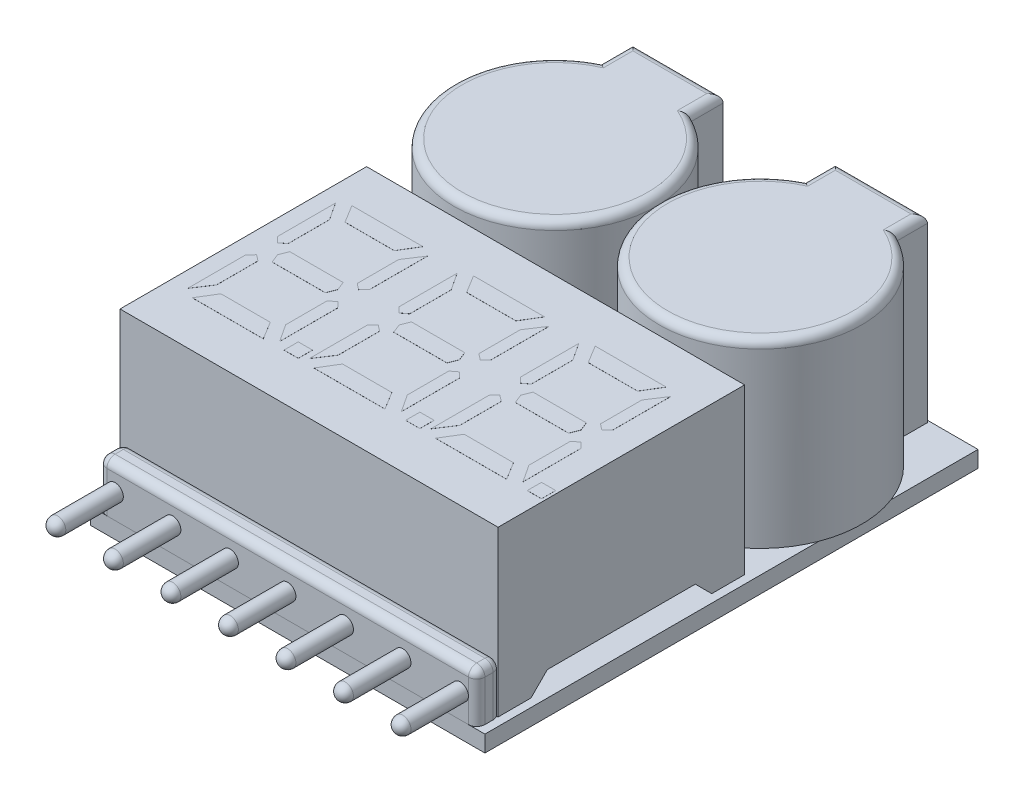
SolidWorks part; units mm, degrees
ref_plane "Ön Düzlem" through (0, 0, 0) normal (0, 0, 1) x (1, 0, 0)
ref_plane "Üst Düzlem" through (0, 0, 0) normal (0, 1, 0) x (1, 0, 0)
ref_plane "Sağ Düzlem" through (0, 0, 0) normal (1, 0, 0) x (0, 0, -1)
sketch "Çizim1" plane through (0, 0, 0) normal (0, 1, 0) x (1, 0, 0)
  line L1 (12, -20) -> (-12, -20)
  line L2 (12, -20) -> (12, 20)
  line L3 (12, 20) -> (-12, 20)
  line L4 (-12, -20) -> (-12, 20)
  line L5 (12, -20) -> (-12, 20) construction
  line L6 (12, 20) -> (-12, -20) construction
  point P0 (0, 0)
  dimension "D1" = 40
  dimension "D2" = 24
extrude "Yükseklik-Ekstrüzyon1" add sketch "Çizim1" along normal blind 1
sketch "Çizim2" plane through (0, 1, 0) normal (0, 1, 0) x (1, 0, 0)
  line L1 (-11.5, -10) -> (11.5, -10)
  line L2 (-11.5, -10) -> (-11.5, -8.5)
  line L3 (-11.5, -8.5) -> (11.5, -8.5)
  line L4 (11.5, -10) -> (11.5, -8.5)
  line L5 (-12, 20) -> (-12, -20) construction
  line L6 (12, -20) -> (12, 20) construction
  line L8 (12, 20) -> (-12, 20) construction
  dimension "D1" = 0.5
  dimension "D2" = 0.5
  dimension "D3" = 1.5
  dimension "D4" = 28.5
  dimension "D5" = 1.5
extrude "Yükseklik-Ekstrüzyon2" add sketch "Çizim2" along normal blind 3 separate body
sketch "Çizim3" plane through (0, 0, 10) normal (0, 0, 1) x (1, 0, 0)
  line L0 (-11.5, 2.5) -> (11.5, 2.5) construction
  line L1 (-11.5, 4) -> (-11.5, 1) construction
  line L2 (11.5, 4) -> (11.5, 1) construction
  line L3 (-8, 2.5) -> (15, 2.5) construction
  line L4 (-4.5, 2.5) -> (18.5, 2.5) construction
  line L5 (-1, 2.5) -> (22, 2.5) construction
  line L6 (-15, 2.5) -> (8, 2.5) construction
  line L7 (-18.5, 2.5) -> (4.5, 2.5) construction
  line L8 (-22, 2.5) -> (1, 2.5) construction
  circle A0 centre (0, 2.5) radius 0.5
  circle A1 centre (3.5, 2.5) radius 0.5
  circle A2 centre (7, 2.5) radius 0.5
  circle A3 centre (10.5, 2.5) radius 0.5
  circle A4 centre (-3.5, 2.5) radius 0.5
  circle A5 centre (-7, 2.5) radius 0.5
  circle A6 centre (-10.5, 2.5) radius 0.5
  dimension "D1" = 1
  dimension "D2" = 4
  dimension "D3" = 4
extrude "Yükseklik-Ekstrüzyon3" add sketch "Çizim3" along normal blind 4
sketch "Çizim4" plane through (0, 1, 0) normal (0, 1, 0) x (1, 0, 0)
  line L0 (12, 20) -> (-12, 20) construction
  line L1 (-11.5, -8.7) -> (11.5, -8.7)
  line L2 (-11.5, -8.7) -> (-11.5, 6.3)
  line L3 (-11.5, 6.3) -> (11.5, 6.3)
  line L4 (11.5, -8.7) -> (11.5, 6.3)
  line L5 (-11.5, -8.7) -> (11.5, 6.3) construction
  line L6 (-11.5, 6.3) -> (11.5, -8.7) construction
  line L7 (-12, 20) -> (-12, -20) construction
  line L8 (12, -20) -> (12, 20) construction
  point P0 (0, -1.2)
  dimension "D1" = 15
  dimension "D2" = 23
  dimension "D3" = 13.7
extrude "Yükseklik-Ekstrüzyon4" add sketch "Çizim4" along normal blind 10
sketch "Çizim5" plane through (0, 1, 0) normal (0, 1, 0) x (1, 0, 0)
  line L0 (12, 20) -> (-12, 20) construction
  line L7 (3.4483, 17.9999) -> (3.4483, 19.8699)
  line L9 (-9, 18.026) -> (-9, 20)
  line L10 (-9, 20) -> (-3.5, 20)
  line L11 (-3.5, 18.026) -> (-3.5, 20)
  line L14 (9.0517, 19.8699) -> (3.4483, 19.8699)
  line L15 (9.0517, 17.9999) -> (9.0517, 19.8699)
  arc A0 (-9, 18.026) -> (-3.5, 18.026) centre (-6.25, 12.5175) ccw
  arc A1 (3.4483, 17.9999) -> (9.0517, 17.9999) centre (6.25, 12.5175) ccw
  point P9 (0, 6.418)
  point P16 (-6.25, 18.6743)
  dimension "D1" = 5.5
  dimension "D2" = 1.974
extrude "Yükseklik-Ekstrüzyon10" add sketch "Çizim5" along normal blind 11
sketch "Çizim6" plane through (-11.5, 0, 0) normal (-1, 0, 0) x (0, 0, 1)
  line L0 (6.7, 1) -> (5.7, 2)
  line L1 (-6.3, 1) -> (8.7, 1) construction
  line L2 (5.7, 2) -> (-3.3, 2)
  line L3 (-3.3, 2) -> (-4.3, 1)
  line L4 (6.7, 1) -> (-4.3, 1)
  point P4 (1.2, 1)
  point P7 (1.2, 2)
  dimension "D1" = 2
  dimension "D2" = 1
  dimension "D3" = 135
extrude "Kes-Ekstrüzyon2" cut sketch "Çizim6" against normal blind 40
sketch "Çizim7" plane through (0, 0, 8.7) normal (0, 0, 1) x (1, 0, 0)
  line L0 (-9.5, 1) -> (-8.386, 2)
  line L2 (-12, 1) -> (12, 1) construction
  line L3 (-8.386, 2) -> (8.386, 2)
  line L4 (11.5, 11) -> (11.5, 1) construction
  line L5 (-11.5, 11) -> (-11.5, 1) construction
  line L6 (-11.5, 6) -> (11.5, 6) construction
  line L8 (8.386, 2) -> (9.2837, 1)
  line L9 (-11.5, 1) -> (11.5, 1) construction
  line L10 (-9.5, 1) -> (9.2837, 1)
  line L14 (0, 6) -> (0, 11) construction
  line L15 (-11.5, 11) -> (11.5, 11) construction
  point P5 (0, 2)
  dimension "D1" = 23
  dimension "D2" = 2
  dimension "D3" = 1
extrude "Kes-Ekstrüzyon3" cut sketch "Çizim7" against normal blind 20
fillet "Radyus1" radius 0.5 8 edges at (11.5, 4, 9.25) (0, 4, 10) (11.5, 2.5, 10) (-11.5, 4, 9.25) (-11.5, 2.5, 10) (-11.5, 2.5, 8.5) (0, 4, 8.5) (11.5, 2.5, 8.5)
fillet "Radyus2" radius 0.5 8 edges at (3.4483, 12, -18.9349) (6.25, 12, -19.8699) (9.0517, 12, -18.9349) (6.25, 12, -6.3607) (-9, 12, -19.013) (-6.25, 12, -20) (-3.5, 12, -19.013) (-6.25, 12, -6.3607)
sketch "Çizim8" plane through (0, 11, 0) normal (0, 1, 0) x (1, 0, 0)
  line L0 (-9.3462, -0.5211) -> (-6.1062, -0.5211)
  line L1 (-6.2265, -4.8359) -> (-9.2259, -4.8359)
  line L2 (-9.2259, -4.8359) -> (-9.8862, -5.9159)
  line L3 (-9.8283, -4.498) -> (-10.5232, -5.556)
  line L4 (-10.5232, -5.556) -> (-10.5232, -2.0259)
  line L5 (-9.8283, -4.498) -> (-9.8283, -1.9771)
  line L6 (-10.5232, -2.0259) -> (-10.198, -1.693)
  line L7 (-10.198, -1.693) -> (-9.8283, -1.9771)
  line L8 (-9.3462, -1.6011) -> (-6.1062, -1.6011)
  line L9 (-9.8862, -5.9159) -> (-5.5662, -5.9159)
  line L10 (-4.3393, -5.0178) -> (-3.4753, -5.0178)
  line L11 (-4.3393, -5.0178) -> (-4.3393, -5.8818)
  line L12 (-4.3393, -5.8818) -> (-3.4753, -5.8818)
  line L13 (-9.5601, -1.0611) -> (-9.3462, -0.5211)
  line L14 (-3.4753, -5.0178) -> (-3.4753, -5.8818)
  line L15 (-5.8922, -1.0611) -> (-6.1062, -0.5211)
  line L16 (-5.2544, -1.693) -> (-5.6241, -1.9771)
  line L17 (-4.9291, -2.0259) -> (-5.2544, -1.693)
  line L18 (-5.6241, -4.498) -> (-5.6241, -1.9771)
  line L19 (-4.9291, -5.556) -> (-4.9291, -2.0259)
  line L20 (-5.6241, -4.498) -> (-4.9291, -5.556)
  line L21 (-6.2265, -4.8359) -> (-5.5662, -5.9159)
  line L23 (-2.4862, -5.9159) -> (1.8338, -5.9159)
  line L24 (-5.5662, 3.7938) -> (-9.8862, 3.7938)
  line L25 (4.9138, -5.9159) -> (9.2338, -5.9159)
  line L26 (-9.2259, 2.7138) -> (-6.2265, 2.7138)
  line L27 (-6.2265, 2.7138) -> (-5.5662, 3.7938)
  line L28 (-5.6241, 2.3758) -> (-4.9291, 3.4339)
  line L29 (-4.9291, 3.4339) -> (-4.9291, -0.0963)
  line L30 (-5.6241, 2.3758) -> (-5.6241, -0.1451)
  line L31 (-4.9291, -0.0963) -> (-5.2544, -0.4291)
  line L32 (-5.2544, -0.4291) -> (-5.6241, -0.1451)
  line L33 (1.1735, -4.8359) -> (-1.8259, -4.8359)
  line L34 (-5.8922, -1.0611) -> (-6.1062, -1.6011)
  line L35 (-9.5601, -1.0611) -> (-9.3462, -1.6011)
  line L36 (-1.8259, -4.8359) -> (-2.4862, -5.9159)
  line L37 (5.4538, -1.6011) -> (8.6938, -1.6011)
  line L38 (8.6938, -0.5211) -> (5.4538, -0.5211)
  line L39 (-10.198, -0.4291) -> (-9.8283, -0.1451)
  line L40 (-10.5232, -0.0963) -> (-10.198, -0.4291)
  line L41 (-9.8283, 2.3758) -> (-9.8283, -0.1451)
  line L42 (-10.5232, 3.4339) -> (-10.5232, -0.0963)
  line L43 (-9.8283, 2.3758) -> (-10.5232, 3.4339)
  line L44 (-9.2259, 2.7138) -> (-9.8862, 3.7938)
  line L46 (-2.4283, -4.498) -> (-3.1232, -5.556)
  line L48 (-3.1232, -5.556) -> (-3.1232, -2.0259)
  line L49 (-2.4283, -4.498) -> (-2.4283, -1.9771)
  line L50 (-3.1232, -2.0259) -> (-2.798, -1.693)
  line L51 (-2.798, -1.693) -> (-2.4283, -1.9771)
  line L52 (1.2938, -1.6011) -> (-1.9462, -1.6011)
  line L53 (-1.9462, -0.5211) -> (1.2938, -0.5211)
  line L54 (3.0607, -5.0178) -> (3.9247, -5.0178)
  line L55 (3.0607, -5.0178) -> (3.0607, -5.8818)
  line L56 (3.0607, -5.8818) -> (3.9247, -5.8818)
  line L57 (-2.1601, -1.0611) -> (-1.9462, -0.5211)
  line L58 (3.9247, -5.0178) -> (3.9247, -5.8818)
  line L59 (1.5078, -1.0611) -> (1.2938, -0.5211)
  line L60 (2.1456, -1.693) -> (1.7759, -1.9771)
  line L61 (2.4709, -2.0259) -> (2.1456, -1.693)
  line L62 (1.7759, -4.498) -> (1.7759, -1.9771)
  line L63 (2.4709, -5.556) -> (2.4709, -2.0259)
  line L64 (1.7759, -4.498) -> (2.4709, -5.556)
  line L65 (1.1735, -4.8359) -> (1.8338, -5.9159)
  line L68 (1.8338, 3.7938) -> (-2.4862, 3.7938)
  line L69 (-1.8259, 2.7138) -> (1.1735, 2.7138)
  line L70 (1.1735, 2.7138) -> (1.8338, 3.7938)
  line L71 (1.7759, 2.3758) -> (2.4709, 3.4339)
  line L72 (2.4709, 3.4339) -> (2.4709, -0.0963)
  line L73 (1.7759, 2.3758) -> (1.7759, -0.1451)
  line L74 (2.4709, -0.0963) -> (2.1456, -0.4291)
  line L75 (2.1456, -0.4291) -> (1.7759, -0.1451)
  line L76 (1.5078, -1.0611) -> (1.2938, -1.6011)
  line L77 (-2.1601, -1.0611) -> (-1.9462, -1.6011)
  line L80 (-2.798, -0.4291) -> (-2.4283, -0.1451)
  line L81 (-3.1232, -0.0963) -> (-2.798, -0.4291)
  line L82 (-2.4283, 2.3758) -> (-2.4283, -0.1451)
  line L83 (-3.1232, 3.4339) -> (-3.1232, -0.0963)
  line L84 (-2.4283, 2.3758) -> (-3.1232, 3.4339)
  line L85 (-1.8259, 2.7138) -> (-2.4862, 3.7938)
  line L88 (-11.5, 6.3) -> (11.5, 6.3) construction
  line L94 (8.5735, -4.8359) -> (5.5741, -4.8359)
  line L95 (5.5741, -4.8359) -> (4.9138, -5.9159)
  line L96 (4.9717, -4.498) -> (4.2768, -5.556)
  line L97 (4.2768, -5.556) -> (4.2768, -2.0259)
  line L98 (4.9717, -4.498) -> (4.9717, -1.9771)
  line L99 (4.2768, -2.0259) -> (4.602, -1.693)
  line L100 (4.602, -1.693) -> (4.9717, -1.9771)
  line L103 (10.4607, -5.0178) -> (11.3247, -5.0178)
  line L104 (10.4607, -5.0178) -> (10.4607, -5.8818)
  line L105 (10.4607, -5.8818) -> (11.3247, -5.8818)
  line L106 (5.2399, -1.0611) -> (5.4538, -0.5211)
  line L107 (11.3247, -5.0178) -> (11.3247, -5.8818)
  line L108 (8.9078, -1.0611) -> (8.6938, -0.5211)
  line L109 (9.5456, -1.693) -> (9.1759, -1.9771)
  line L110 (9.8709, -2.0259) -> (9.5456, -1.693)
  line L111 (9.1759, -4.498) -> (9.1759, -1.9771)
  line L112 (9.8709, -5.556) -> (9.8709, -2.0259)
  line L113 (9.1759, -4.498) -> (9.8709, -5.556)
  line L114 (8.5735, -4.8359) -> (9.2338, -5.9159)
  line L117 (9.2338, 3.7938) -> (4.9138, 3.7938)
  line L118 (5.5741, 2.7138) -> (8.5735, 2.7138)
  line L119 (8.5735, 2.7138) -> (9.2338, 3.7938)
  line L120 (9.1759, 2.3758) -> (9.8709, 3.4339)
  line L121 (9.8709, 3.4339) -> (9.8709, -0.0963)
  line L122 (9.1759, 2.3758) -> (9.1759, -0.1451)
  line L123 (9.8709, -0.0963) -> (9.5456, -0.4291)
  line L124 (9.5456, -0.4291) -> (9.1759, -0.1451)
  line L125 (8.9078, -1.0611) -> (8.6938, -1.6011)
  line L126 (5.2399, -1.0611) -> (5.4538, -1.6011)
  line L129 (4.602, -0.4291) -> (4.9717, -0.1451)
  line L130 (4.2768, -0.0963) -> (4.602, -0.4291)
  line L131 (4.9717, 2.3758) -> (4.9717, -0.1451)
  line L132 (4.2768, 3.4339) -> (4.2768, -0.0963)
  line L133 (4.9717, 2.3758) -> (4.2768, 3.4339)
  line L134 (5.5741, 2.7138) -> (4.9138, 3.7938)
  point P5 (6.7908, -7.6093)
  point P55 (-7.7262, -1.0277)
  point P80 (-0.3262, -1.0277)
  point P138 (7.0738, -1.0277)
  point P156 (15.2026, -3.851)
  dimension "D1" = 3
extrude "Yükseklik-Ekstrüzyon11" add sketch "Çizim8" along normal blind 0.005 separate body
fillet "Radyus3" radius 0.5 7 edges at (7.5, 2.5, 14) (4, 2.5, 14) (0.5, 2.5, 14) (-3, 2.5, 14) (-6.5, 2.5, 14) (-10, 2.5, 14) (11, 2.5, 14)
sketch "Sketch1" plane through (0, 1, 0) normal (0, 1, 0) x (1, 0, 0)
  line L0 (-12, 20) -> (-15.5036, 20) construction
  line L1 (-15.5036, 20) -> (-15.5036, -10) construction
  line L2 (-12, 20) -> (-12, 14.7184) construction
  line L3 (-12, -10) -> (12, -10)
  line L4 (-12, -10) -> (-12, -20)
  line L5 (-12, -20) -> (12, -20)
  line L6 (12, -10) -> (12, -20)
  dimension "D1" = 30
extrude "Cut-Extrude1" cut sketch "Sketch1" against normal blind 10
